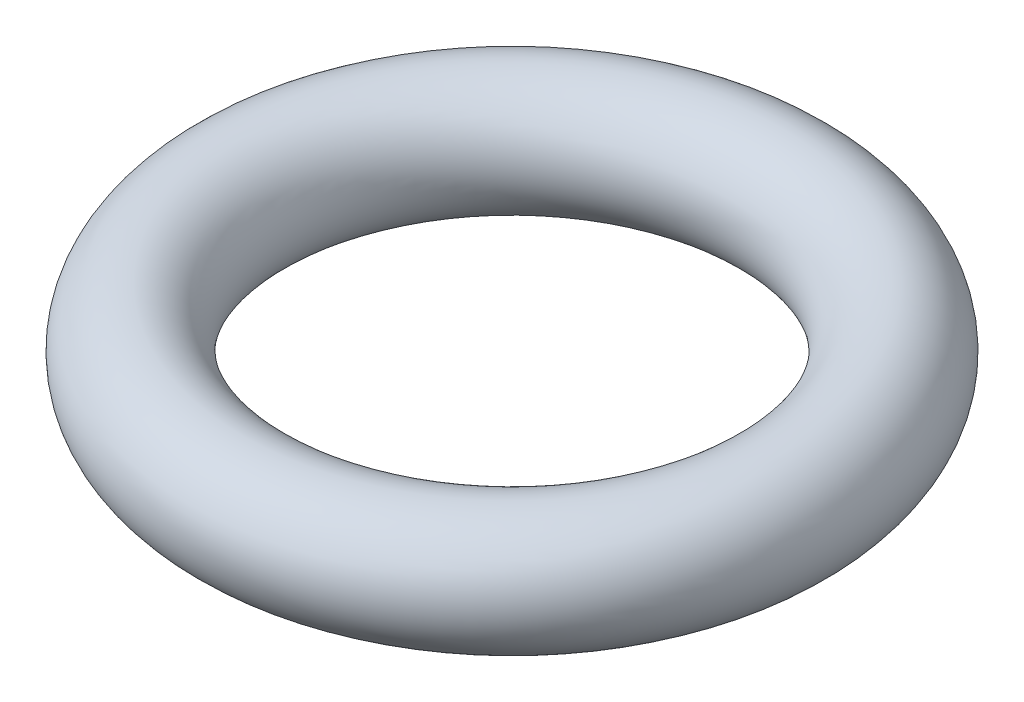
SolidWorks part; units mm, degrees
ref_plane "Front Plane" through (0, 0, 0) normal (0, 0, 1) x (1, 0, 0)
ref_plane "Top Plane" through (0, 0, 0) normal (0, 1, 0) x (1, 0, 0)
ref_plane "Right Plane" through (0, 0, 0) normal (1, 0, 0) x (0, 0, -1)
sketch "Sketch1" plane through (0, 0, 0) normal (0, 1, 0) x (1, 0, 0)
  circle A1 centre (0, 0) radius 4.5974
  dimension "B" = 9.1948
sketch "Sketch2" plane through (0, 0, 0) normal (0, 0, 1) x (1, 0, 0)
  circle A0 centre (-5.9055, 0) radius 1.3081
  point P4 (-4.5974, 0)
  dimension "A" = 2.6162
sweep "Sweep1" add profiles "Sketch2" path "Sketch1"
ref_axis "Axis1" through (0, 5.2562, 0) along (0, -1, 0)
